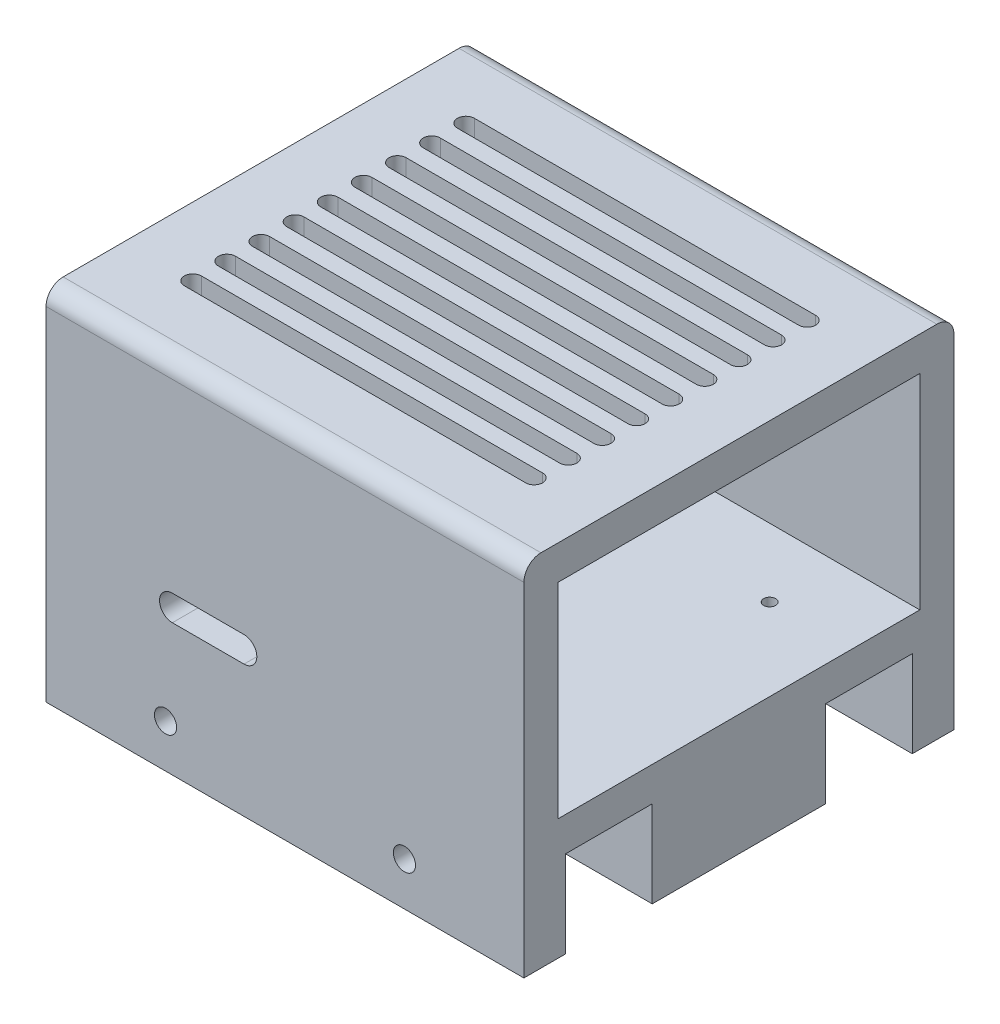
SolidWorks part; units mm, degrees
material "PETG"
ref_plane "Front Plane" through (0, 0, 0) normal (0, 0, 1) x (1, 0, 0)
ref_plane "Top Plane" through (0, 0, 0) normal (0, 1, 0) x (1, 0, 0)
ref_plane "Right Plane" through (0, 0, 0) normal (1, 0, 0) x (0, 0, -1)
sketch "Sketch1" plane through (0, 0, 0) normal (0, 1, 0) x (1, 0, 0)
  line L0 (-57.3, 38.1) -> (-70, 38.1) construction
  line L1 (-70, -25.395) -> (70, -25.395)
  line L2 (-70, -25.395) -> (-70, 25.395)
  line L3 (-70, 25.395) -> (70, 25.395)
  line L4 (70, -25.395) -> (70, 25.395)
  line L5 (-70, 52.5) -> (70, 52.5)
  line L6 (-70, 52.5) -> (-70, -52.5)
  line L7 (-70, -52.5) -> (70, -52.5)
  line L8 (70, 52.5) -> (70, -52.5)
  line L11 (57.3, 38.1) -> (70, 38.1) construction
  circle A0 centre (-57.3, 38.1) radius 3.25
  circle A1 centre (57.3, 38.1) radius 3.25
  circle A2 centre (-57.3, -38.1) radius 3.25
  circle A3 centre (57.3, -38.1) radius 3.25
  point P4 (-70, 0)
  point P5 (0, 25.395)
  point P19 (0, 0)
  dimension "D4" = 6.5
  dimension "D1" = 50.79
  dimension "D2" = 140
  dimension "D3" = 105
  dimension "D5" = 38.1
  dimension "D6" = 12.7
  dimension "D7" = 38.1
extrude "Boss-Extrude1" add sketch "Sketch1" along normal blind 10 contours L1 L4 L3 L2 | L8 L1 L6 L7 | L8 L5 L6 L3 | A1 | A0 | A2 | A3 region at (0, 0, 0) region at (0, 0, 38.9626) region at (0, 0, -38.9626) region at (-57.3, 0, -38.1) region at (57.3, 0, -38.1) region at (-57.3, 0, 38.1) region at (57.3, 0, 38.1)
extrude "Boss-Extrude2" add sketch "Sketch1<3>" against normal blind 25.4 contours L1 L4 L3 L2 region at (0, 0, 0)
sketch "Sketch1<3>" plane through (0, 0, 0) normal (0, 1, 0) x (1, 0, 0) same geometry as "Sketch1"
sketch "Sketch2" plane through (0, 10, 0) normal (0, 1, 0) x (1, 0, 0)
  line L0 (-46, 33) -> (-46, -46) construction
  line L1 (-46, -46) -> (46, -46) construction
  line L2 (46, -46) -> (46, 33) construction
  line L3 (46, 33) -> (-46, 33) construction
  line L4 (-70, -52.5) -> (70, -52.5) construction
  line L6 (-70, 52.5) -> (70, 52.5) construction
  line L7 (46, 0) -> (-46, 0) construction
  circle A0 centre (-46, 33) radius 4.5
  circle A1 centre (-46, 33) radius 1.75
  circle A2 centre (46, 33) radius 4.5
  circle A3 centre (46, 33) radius 1.75
  circle A4 centre (46, -46) radius 4.5
  circle A5 centre (46, -46) radius 1.75
  circle A6 centre (-46, -46) radius 4.5
  circle A7 centre (-46, -46) radius 1.75
  point P19 (0, 0)
  dimension "D1" = 3.5
  dimension "D2" = 9
  dimension "D3" = 6.5
  dimension "D4" = 92
  dimension "D5" = 19.5
extrude "Cut-Extrude4" cut sketch "Sketch2" against normal up to next contours A1 | A3 | A5 | A7 region at (-46, 10, -33)
sketch "Sketch3" plane through (0, 0, 0) normal (0, 1, 0) x (1, 0, 0)
  circle A0 centre (-46, 33) radius 3.2
  circle A1 centre (46, 33) radius 3.2
  circle A2 centre (46, -46) radius 3.2
  circle A3 centre (-46, -46) radius 3.2
  point P2 (-36.2719, 34.0929)
  point P5 (0, 0)
  point P12 (0, 0)
  point P13 (-36.4778, 32.6516)
  point P14 (-46, 33)
  point P15 (46, 33)
  point P16 (0, 0)
  point P17 (28.7581, 40.7154)
  point P18 (46, -46)
  point P19 (0, 0)
  point P20 (-46, -46)
  point P22 (0, 0)
  point P25 (0, 0)
  dimension "D1" = 6.4
extrude "Cut-Extrude3" cut sketch "Sketch3" along normal offset from surface (6.5 mm away) 3.5 up to face at (-46, 10, 47.75)
sketch "Sketch5" plane through (-70, 0, 0) normal (-1, 0, 0) x (0, 0, 1)
  line L0 (52.5, 10) -> (-52.5, 10) construction
  line L1 (-53, 0) -> (-63, 0)
  line L2 (-53, 0) -> (-53, 80)
  line L3 (-53, 80) -> (-63, 80)
  line L4 (-63, 0) -> (-63, 80)
  line L6 (-52.5, 10) -> (-53, 10)
  line L7 (53, 0) -> (63, 0)
  line L8 (53, 0) -> (53, 80)
  line L9 (53, 80) -> (63, 80)
  line L10 (63, 0) -> (63, 80)
  line L11 (-52.5, 10) -> (-52.5, 0)
  line L12 (-52.5, 0) -> (-53, 0)
  line L13 (-53, 80) -> (53, 80)
  line L14 (-53, 80) -> (-53, 70)
  line L15 (-53, 70) -> (53, 70)
  line L16 (53, 80) -> (53, 70)
  line L17 (-53, 10) -> (-53, 0)
  line L18 (52.5, 10) -> (53, 10)
  line L19 (52.5, 10) -> (52.5, 0)
  line L20 (52.5, 0) -> (53, 0)
  line L21 (53, 10) -> (53, 0)
  point P10 (52.5, 0)
  line M9 (52.5, 0) -> (52.5, 10)
  line M11 (-52.5, 10) -> (-52.5, 0)
  dimension "D1" = 10
  dimension "D2" = 60
  dimension "D3" = 0.5
extrude "Boss-Extrude3" add sketch "Sketch5" against normal up to surface (140 mm away) contours L4 L1 L2 L3 | L12 L6 L2 M11 | L2 L15 L8 L13 | L7 L10 L9 L8 | L20 L8 L18 M9 region at (-70, 40, -58) region at (-70, 5, -52.75) region at (-70, 75, 0) region at (-70, 40, 58) region at (-70, 5, 52.75) up to face at (70, -3.85, 0)
sketch "Sketch6" plane through (0, 0, 63) normal (0, 0, 1) x (1, 0, 0)
  line L0 (-33, 17) -> (-12, 17) construction
  line L1 (-33, 20.75) -> (-12, 20.75)
  line L2 (-33, 13.25) -> (-12, 13.25)
  line L3 (-70, 0) -> (-70, 80) construction
  line L4 (70, 0) -> (-70, 0) construction
  arc A0 (-33, 20.75) -> (-33, 13.25) centre (-33, 17) ccw
  arc A1 (-12, 13.25) -> (-12, 20.75) centre (-12, 17) ccw
  point P2 (-22.5, 17)
  point P9 (0, 0)
  dimension "D1" = 37
  dimension "D2" = 21
  dimension "D3" = 7.5
  dimension "17" = 17
extrude "Cut-Extrude6" cut sketch "Sketch6" against normal up to next
sketch "Sketch7" plane through (-70, 0, 0) normal (-1, 0, 0) x (0, 0, 1)
  line L0 (-25.395, 0) -> (-63, 0) construction
  line L1 (-63, 0) -> (-50.805, 0)
  line L2 (-63, 0) -> (-63, -25.4)
  line L3 (-63, -25.4) -> (-50.805, -25.4)
  line L4 (-50.805, 0) -> (-50.805, -25.4)
  line L5 (25.395, -25.4) -> (-25.395, -25.4) construction
  line L6 (-25.395, -25.4) -> (-25.395, 0) construction
  line L8 (63, 0) -> (50.805, 0)
  line L9 (63, 0) -> (63, -25.4)
  line L10 (63, -25.4) -> (50.805, -25.4)
  line L11 (50.805, 0) -> (50.805, -25.4)
  dimension "D1" = 25.41
extrude "Boss-Extrude4" add sketch "Sketch7" against normal up to surface (140 mm away) up to face at (70, 13.65, 0)
sketch "Sketch8" plane through (0, 0, -63) normal (0, 0, -1) x (-1, 0, 0)
  line L0 (-70, -25.4) -> (70, -25.4) construction
  line L1 (-70, 80) -> (-70, -25.4) construction
  line L2 (0, 0) -> (0, 50000) construction
  circle A0 centre (-35, -12.7) radius 3.25
  circle A2 centre (35, -12.7) radius 3.25
  dimension "D1" = 6.5
  dimension "D2" = 12.7
  dimension "D3" = 35
extrude "Cut-Extrude7" cut sketch "Sketch8" against normal up to next
mirror "Mirror1" about plane through (0, 0, 0) normal (0, 0, 1) of "Cut-Extrude7"
fillet "Fillet1" radius 5 2 edges at (0, 80, 63) (0, 80, -63)
sketch "Sketch9" plane through (0, 80, 0) normal (0, 1, 0) x (1, 0, 0)
  line L0 (-50, 40) -> (50, 40) construction
  line L1 (-50, 42.5) -> (50, 42.5)
  line L2 (-50, 37.5) -> (50, 37.5)
  line L3 (-50, 30) -> (50, 30) construction
  line L4 (-50, 32.5) -> (50, 32.5)
  line L5 (-50, 27.5) -> (50, 27.5)
  line L6 (-50, 20) -> (50, 20) construction
  line L7 (-50, 22.5) -> (50, 22.5)
  line L8 (-50, 17.5) -> (50, 17.5)
  line L9 (-50, 10) -> (50, 10) construction
  line L10 (-50, 12.5) -> (50, 12.5)
  line L11 (-50, 7.5) -> (50, 7.5)
  line L12 (-50, 0) -> (50, 0) construction
  line L13 (-50, 2.5) -> (50, 2.5)
  line L14 (-50, -2.5) -> (50, -2.5)
  line L15 (-50, -10) -> (50, -10) construction
  line L16 (-50, -7.5) -> (50, -7.5)
  line L17 (-50, -12.5) -> (50, -12.5)
  line L18 (-50, -20) -> (50, -20) construction
  line L19 (-50, -17.5) -> (50, -17.5)
  line L20 (-50, -22.5) -> (50, -22.5)
  line L21 (-50, 40) -> (-50, 30) construction
  line L22 (-50, -30) -> (50, -30) construction
  line L23 (-50, -27.5) -> (50, -27.5)
  line L24 (-50, -32.5) -> (50, -32.5)
  line L25 (-50, -40) -> (50, -40) construction
  line L26 (-50, -37.5) -> (50, -37.5)
  line L27 (-50, -42.5) -> (50, -42.5)
  arc A0 (-50, 42.5) -> (-50, 37.5) centre (-50, 40) ccw
  arc A1 (50, 37.5) -> (50, 42.5) centre (50, 40) ccw
  arc A2 (-50, 32.5) -> (-50, 27.5) centre (-50, 30) ccw
  arc A3 (50, 27.5) -> (50, 32.5) centre (50, 30) ccw
  arc A4 (-50, 22.5) -> (-50, 17.5) centre (-50, 20) ccw
  arc A5 (50, 17.5) -> (50, 22.5) centre (50, 20) ccw
  arc A6 (-50, 12.5) -> (-50, 7.5) centre (-50, 10) ccw
  arc A7 (50, 7.5) -> (50, 12.5) centre (50, 10) ccw
  arc A8 (-50, 2.5) -> (-50, -2.5) centre (-50, 0) ccw
  arc A9 (50, -2.5) -> (50, 2.5) centre (50, 0) ccw
  arc A10 (-50, -7.5) -> (-50, -12.5) centre (-50, -10) ccw
  arc A11 (50, -12.5) -> (50, -7.5) centre (50, -10) ccw
  arc A12 (-50, -17.5) -> (-50, -22.5) centre (-50, -20) ccw
  arc A13 (50, -22.5) -> (50, -17.5) centre (50, -20) ccw
  arc A14 (-50, -27.5) -> (-50, -32.5) centre (-50, -30) ccw
  arc A15 (50, -32.5) -> (50, -27.5) centre (50, -30) ccw
  arc A16 (-50, -37.5) -> (-50, -42.5) centre (-50, -40) ccw
  arc A17 (50, -42.5) -> (50, -37.5) centre (50, -40) ccw
  point P2 (0, 40)
  point P10 (0, 30)
  point P19 (0, 20)
  point P26 (0, 10)
  point P33 (0, 0)
  point P40 (0, -10)
  point P47 (0, -20)
  point P54 (0, -30)
  point P61 (0, -40)
  dimension "D1" = 100
  dimension "D2" = 5
  dimension "D3" = 40
  dimension "D5" = 10
  dimension "D4" = 9
extrude "Cut-Extrude8" cut sketch "Sketch9" against normal up to next
equation "\"tol_dia_id_intfc\" = 0.0200mm ' For hole diameters - Interference fit"
equation "\"tol_dia_id_slip\"  = 0.0300mm ' For hole diameters - Slip fit"
equation "\"tol_dia_id_clear\" = 0.0500mm ' For hole diameters - Clearance fit"
equation "\"tol_dia_od_intfc\" = 0.0200mm ' For shaft diameters - Interference fit"
equation "\"tol_dia_od_slip\"  = 0.0300mm ' For shaft diameters - Slip fit"
equation "\"tol_dia_od_clear\" = 0.0500mm ' For shaft diameters - Clearance fit"
equation "\"tol_general_intfc\"= 0.0030mm ' For general parts (Horiz) - Interference fit"
equation "\"tol_general_slip\" = 0.0050mm ' For general parts (Horiz) - Slip fit"
equation "\"tol_general_clear\"= 0.0100mm ' For general parts (Horiz) - Clearance fit"
equation "\"tol_layer_intfc\"  = 0.0030mm ' For all parts (Vert) - Interference fit"
equation "\"tol_layer_slip\"   = 0.0050mm ' For all parts (Vert) - Slip fit"
equation "\"tol_layer_clear\"  = 0.0100mm ' For all parts (Vert) - Clearance fit"
equation "\"tol_corner_rad\"   = 0.100mm ' For corners that fit into other parts"
equation "\"D1@Sketch1\"=50.80mm-\"tol_general_slip\"*2"
equation "\"D1@Sketch7\"=1in+\"tol_general_slip\"*2"
